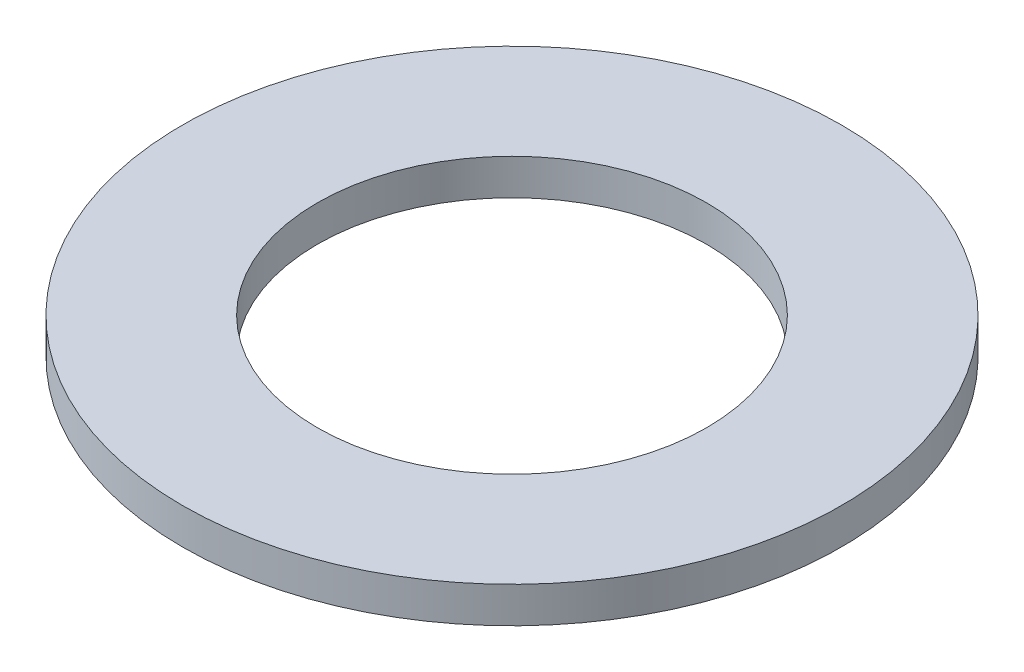
SolidWorks part; units mm, degrees
ref_plane "Front Plane" through (0, 0, 0) normal (0, 0, 1) x (1, 0, 0)
ref_plane "Top Plane" through (0, 0, 0) normal (0, 1, 0) x (1, 0, 0)
ref_plane "Right Plane" through (0, 0, 0) normal (1, 0, 0) x (0, 0, -1)
sketch "Sketch1" plane through (0, 0, 0) normal (0, 1, 0) x (1, 0, 0)
  circle A0 centre (0, 0) radius 55
  dimension "FLANGE_OD" = 110
extrude "Boss-Extrude1" add sketch "Sketch1" along normal blind 6
sketch "Sketch2" plane through (0, 0, 0) normal (0, 1, 0) x (1, 0, 0)
  circle A0 centre (0, 0) radius 32.5
  dimension "BORE_D" = 65
extrude "Cut-Extrude1" cut sketch "Sketch2" along normal through all
sketch "Sketch3" plane through (0, 6, 0) normal (0, 1, 0) x (1, 0, 0)
  circle A0 centre (0, 0) radius 20.7064 construction
  circle A1 centre (-20.7064, 0) radius 3.9898
  dimension "BOLT_D" = 7.9796
  dimension "BOLT_PCD" = 41.4128
extrude "Cut-Extrude2" cut sketch "Sketch3" against normal blind 3.6528 rebuild error yes
pattern_circular "CirPattern1" count 8 over 360 rebuild error yes
